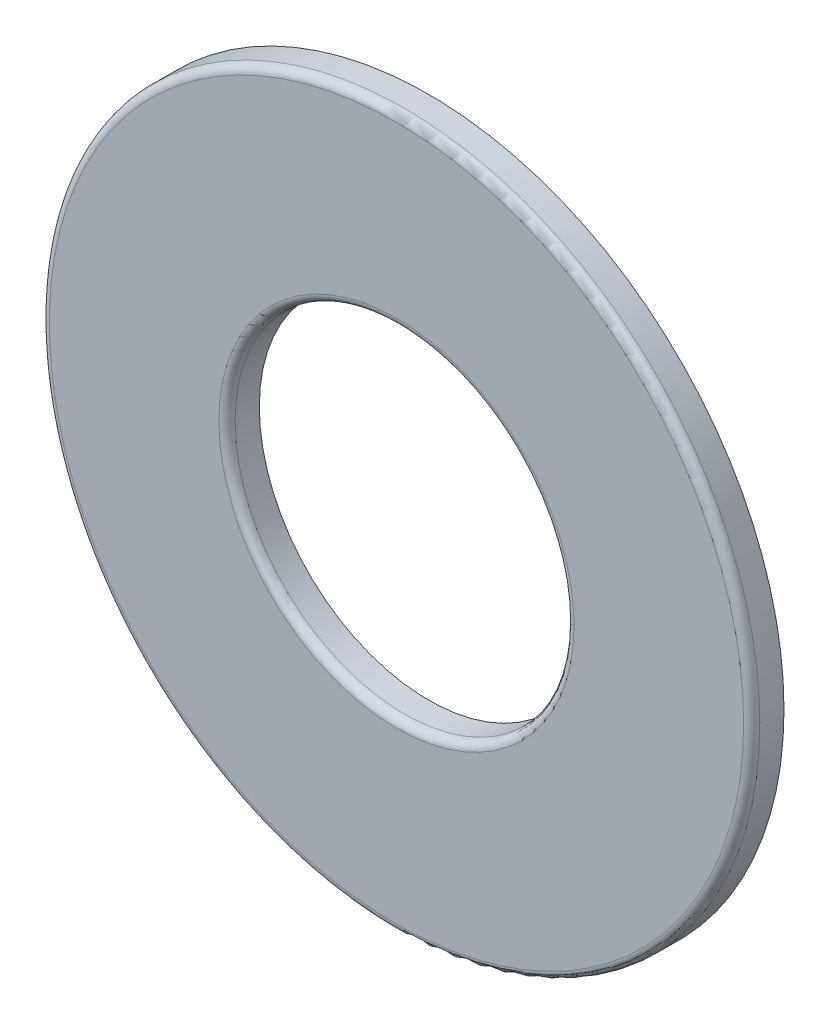
SolidWorks part; units mm, degrees
note: '?' marks a value the reader was unsure of.
other "Imported1" parameters "D1"=0.7937, "TH"=1.0287, "Thickness"=3.175
ref_plane "Front Plane" through (0, 0, 0) normal (0, 0, 1) x (1, 0, 0)
ref_plane "Top Plane" through (0, 0, 0) normal (0, 1, 0) x (1, 0, 0)
ref_plane "Right Plane" through (0, 0, 0) normal (1, 0, 0) x (0, 0, -1)
sketch "Sketch1" plane through (0, 0, 0) normal (0, 0, 1) x (1, 0, 0)
  line L0 (-34.925, 0) -> (34.925, 0) construction
  line L1 (-16.6624, 0) -> (16.6624, 0) construction
  circle A0 centre (0, 0) radius 16.6624 construction
  circle A1 centre (0, 0) radius 34.925 construction
  point P8 (0, 0)
  point P9 (0, 34.925)
  point P11 (16.6624, 0)
  dimension "ID" = 33.3248
  dimension "OD" = 69.85
sketch "Sketch2" plane through (0, 0, 0) normal (1, 0, 0) x (0, 0, -1)
  line L0 (-1.5875, 34.925) -> (1.5875, 34.925) construction
  point P2 (0, 34.925)
sketch "Sketch3" plane through (0, 0, 0) normal (0, 0, 1) x (1, 0, 0)
  circle A0 centre (0, 0) radius 16.6624
  circle A1 centre (0, 0) radius 34.925
extrude "Boss-Extrude1" add sketch "Sketch3" along normal up to vertex (1.5875 mm away) and the other way up to vertex (1.5875 mm away) up to point (0, 34.925, 1.5875) other way up to point (0, 34.925, -1.5875)
fillet "Fillet1" radius 0.7937 2 edges at (34.925, 0, 1.5875) (16.6624, 0, 1.5875)
ref_axis "Center Axis 1" through (0, 0, 0.7938) along (0, 0, -1)?
equation "\"D1@Fillet1\"=\"Thickness@Sketch2\"/4"
